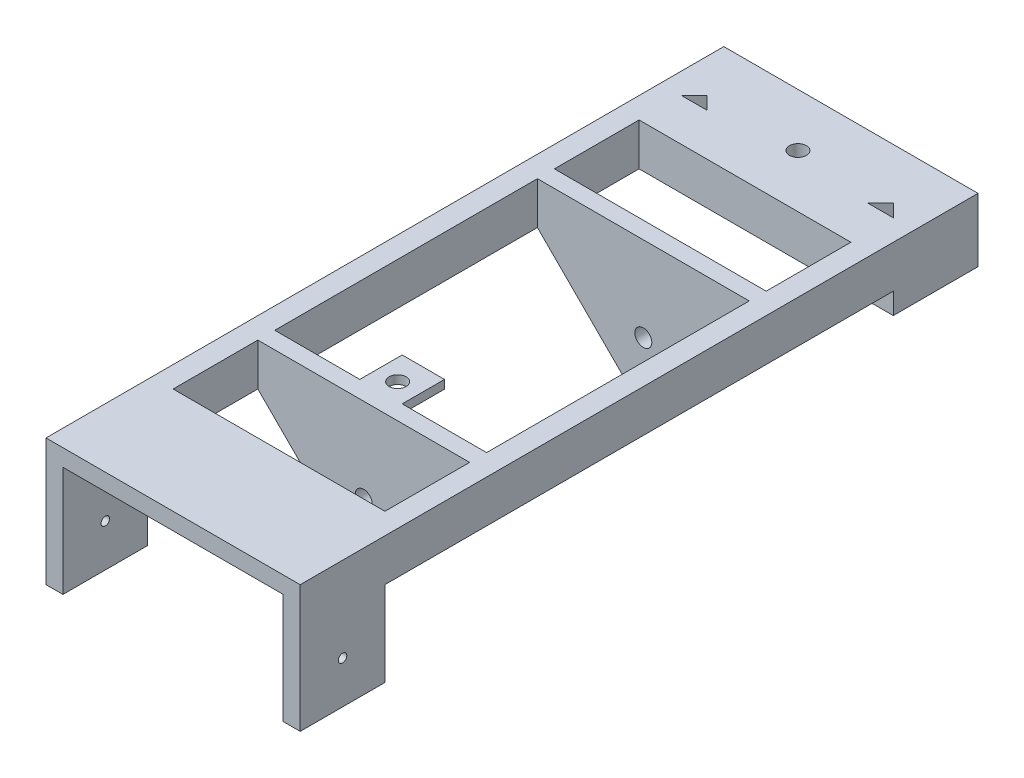
SolidWorks part; units mm, degrees
other "Markup1"
sketch "Sketch19" plane through (-15, 15, -40) normal (-0.0389, 0.0826, -0.9958) x (-0.519, -0.8533, -0.0505)
ref_plane "Front Plane" through (0, 0, 0) normal (0, 0, 1) x (1, 0, 0)
ref_plane "Top Plane" through (0, 0, 0) normal (0, 1, 0) x (1, 0, 0)
ref_plane "Right Plane" through (0, 0, 0) normal (1, 0, 0) x (0, 0, -1)
sketch "Sketch1" plane through (0, 0, 0) normal (0, 1, 0) x (1, 0, 0)
  line L1 (-15, 40) -> (15, 40)
  line L2 (-15, 40) -> (-15, -40)
  line L3 (-15, -40) -> (15, -40)
  line L4 (15, 40) -> (15, -40)
  line L5 (-15, 40) -> (15, -40) construction
  line L6 (-15, -40) -> (15, 40) construction
  point P0 (0, 0)
  dimension "D1" = 30
  dimension "D2" = 80
extrude "Boss-Extrude1" add sketch "Sketch1" along normal blind 5
sketch "Sketch2" plane through (15, 0, 0) normal (1, 0, 0) x (0, 0, -1)
  line L1 (-40, 0) -> (-30, 0)
  line L2 (-40, 0) -> (-40, -10)
  line L3 (-40, -10) -> (-30, -10)
  line L4 (-30, 0) -> (-30, -10)
  line L5 (40, 0) -> (30, 0)
  line L6 (40, 0) -> (40, -10)
  line L7 (40, -10) -> (30, -10)
  line L8 (30, 0) -> (30, -10)
  dimension "D1" = 10
  dimension "D2" = 10
  dimension "D3" = 10
  dimension "D4" = 10
extrude "Boss-Extrude2" add sketch "Sketch2" against normal blind 30
sketch "Sketch3" plane through (15, 0, 0) normal (1, 0, 0) x (0, 0, -1)
  line L0 (-40, 5) -> (-40, -10) construction
  line L2 (-40, -10) -> (-30, -10) construction
  line L15 (40, 5) -> (40, -10) construction
  line L16 (30, -10) -> (40, -10)
  line L17 (30, -10) -> (30, -2.5)
  line L18 (30, -2.5) -> (40, -2.5)
  line L19 (40, -10) -> (40, -2.5)
  circle A0 centre (-35, -5) radius 0.5
  dimension "D1" = 1
  dimension "D2" = 7.5
  dimension "D3" = 5
  dimension "D4" = 5
extrude "Cut-Extrude1" cut sketch "Sketch3" against normal through all both and the other way through all
sketch "Sketch4" plane through (0, 5, 0) normal (0, 1, 0) x (1, 0, 0)
  line L9 (-12.5, -27.5) -> (12.5, -27.5)
  line L10 (-12.5, -27.5) -> (-12.5, 27.5)
  line L11 (-12.5, 27.5) -> (12.5, 27.5)
  line L12 (12.5, -27.5) -> (12.5, 27.5)
  line L13 (-12.5, -27.5) -> (12.5, 27.5) construction
  line L14 (-12.5, 27.5) -> (12.5, -27.5) construction
  point P0 (0, 0)
  dimension "D1" = 55
  dimension "D2" = 25
extrude "Cut-Extrude2" cut sketch "Sketch4" against normal through all both and the other way through all
sketch "Sketch20" plane through (0, 5, 0) normal (0, 1, 0) x (1, 0, 0)
  line L0 (11, 34) -> (9.5, 32.5)
  line L1 (11, 34) -> (12.5, 32.5)
  line L2 (9.5, 32.5) -> (12.5, 32.5)
  line L3 (-11, 34) -> (-12.5, 32.5)
  line L4 (-11, 34) -> (-9.5, 32.5)
  line L5 (-12.5, 32.5) -> (-9.5, 32.5)
  line L6 (-15, 40) -> (-15, -40) construction
  line L7 (15, -40) -> (15, 40) construction
  line L9 (12.5, 27.5) -> (-12.5, 27.5) construction
  dimension "D1" = 3
  dimension "D2" = 3
  dimension "D3" = 5
  dimension "D4" = 5
  dimension "D5" = 2.5
  dimension "D6" = 2.5
extrude "Cut-Extrude4" cut sketch "Sketch20" against normal through all both and the other way through all
sketch "Sketch21" plane through (0, 5, 0) normal (0, 1, 0) x (1, 0, 0)
  line L0 (12.5, 27.5) -> (-12.5, 27.5) construction
  line L1 (-15, 40) -> (-15, -40) construction
  circle A0 centre (0, 33.75) radius 1
  dimension "D1" = 2
  dimension "D2" = 6.25
  dimension "D3" = 15
extrude "Cut-Extrude5" cut sketch "Sketch21" against normal through all both and the other way through all
sketch "Sketch22" plane through (0, 0, 40) normal (0, 0, 1) x (1, 0, 0)
  line L0 (-15, -10) -> (15, -10) construction
  line L1 (-13, -10) -> (13, -10)
  line L2 (-13, -10) -> (-13, 3)
  line L3 (-13, 3) -> (13, 3)
  line L4 (13, -10) -> (13, 3)
  line L5 (-15, 5) -> (15, 5) construction
  line L6 (-15, 5) -> (-15, -10) construction
  line L7 (15, 5) -> (15, -10) construction
  dimension "D1" = 2
  dimension "D2" = 2
  dimension "D3" = 2
extrude "Cut-Extrude6" cut sketch "Sketch22" against normal up to surface (10 mm away) up to face at (0, -5, 30)
sketch "Sketch23" plane through (0, 5, 0) normal (0, 1, 0) x (1, 0, 0)
  line L0 (-12.5, 27.5) -> (-12.5, -27.5) construction
  line L1 (-12.5, 15.5) -> (12.5, 15.5)
  line L2 (-12.5, 15.5) -> (-12.5, 17.5)
  line L3 (-12.5, 17.5) -> (12.5, 17.5)
  line L4 (12.5, 15.5) -> (12.5, 17.5)
  line L5 (12.5, -27.5) -> (12.5, 27.5) construction
  line L6 (12.5, 27.5) -> (-12.5, 27.5) construction
  line L7 (-12.5, -17.5) -> (12.5, -17.5)
  line L8 (-12.5, -17.5) -> (-12.5, -15.5)
  line L9 (-12.5, -15.5) -> (12.5, -15.5)
  line L10 (12.5, -17.5) -> (12.5, -15.5)
  line L11 (-12.5, -27.5) -> (12.5, -27.5) construction
  dimension "D1" = 2
  dimension "D2" = 2
  dimension "D3" = 10
  dimension "D4" = 10
extrude "Boss-Extrude3" add sketch "Sketch23" against normal blind 15
sketch "Sketch24" plane through (0, 0, 17.5) normal (0, 0, 1) x (1, 0, 0)
  line L0 (-12.5, -10) -> (12.5, -10) construction
  line L1 (-12.5, -10) -> (-12.5, 0) construction
  circle A0 centre (0, -5) radius 1
  dimension "D1" = 2
  dimension "D2" = 5
  dimension "D3" = 12.5
extrude "Cut-Extrude7" cut sketch "Sketch24" against normal up to surface (35 mm away) contours A0 up to face at (0, -1.6667, -17.5)
chamfer "Chamfer1" distance 10 angle 45 4 edges at (-12.5, -10, 16.5) (12.5, -10, 16.5) (-12.5, -10, -16.5) (12.5, -10, -16.5)
sketch "Sketch25" plane through (0, 5, 0) normal (0, 1, 0) x (1, 0, 0)
  line L5 (12.5, -15.5) -> (-12.5, -15.5) construction
  line L6 (-2.4635, -15.5) -> (2.5365, -15.5)
  line L7 (-2.4635, -15.5) -> (-2.4635, -10.5)
  line L8 (-2.4635, -10.5) -> (2.5365, -10.5)
  line L9 (2.5365, -15.5) -> (2.5365, -10.5)
  line L10 (-2.4635, -15.5) -> (2.5365, -10.5) construction
  line L11 (-2.4635, -10.5) -> (2.5365, -15.5) construction
  point P0 (0, 0)
  point P1 (0.0365, -13)
  dimension "D1" = 5
  dimension "D2" = 5
  dimension "D3" = 0
extrude "Boss-Extrude4" add sketch "Sketch25" against normal blind 1
sketch "Sketch26" plane through (0, 5, 0) normal (0, 1, 0) x (1, 0, 0)
  line L0 (-2.4635, -15.5) -> (-12.5, -15.5) construction
  circle A0 centre (0, -13.5) radius 1
  dimension "D1" = 2
  dimension "D2" = 2
extrude "Cut-Extrude8" cut sketch "Sketch26" against normal through all both and the other way through all
equation "\"w\"=3.9113"
